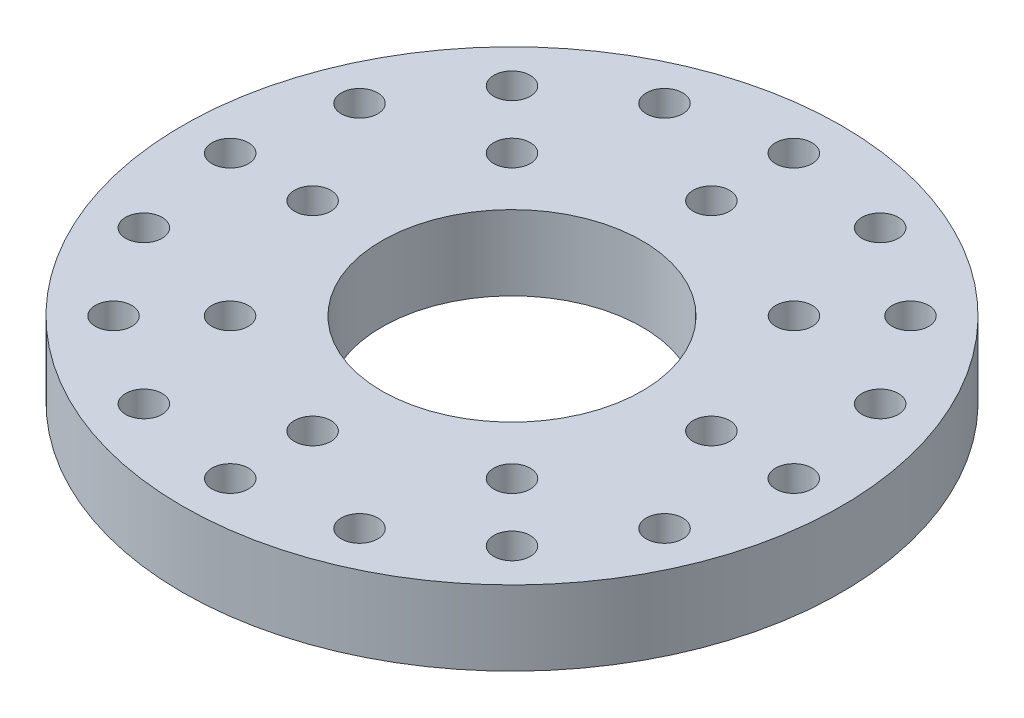
SolidWorks part; units mm, degrees
ref_plane "Front Plane" through (0, 0, 0) normal (0, 0, 1) x (1, 0, 0)
ref_plane "Top Plane" through (0, 0, 0) normal (0, 1, 0) x (1, 0, 0)
ref_plane "Right Plane" through (0, 0, 0) normal (1, 0, 0) x (0, 0, -1)
sketch "Sketch1" plane through (0, 0, 0) normal (0, 1, 0) x (1, 0, 0)
  circle A0 centre (0, 0) radius 76.2
  dimension "D1" = 152.4
extrude "Extrude1" add sketch "Sketch1" along normal blind 17.272
sketch "Sketch2" plane through (0, 0, 0) normal (0, 1, 0) x (1, 0, 0)
  circle A0 centre (0, 0) radius 30.099
  dimension "D1" = 60.198
extrude "Cut-Extrude1" cut sketch "Sketch2" along normal blind 22.352
sketch "Sketch3" plane through (0, 0, 0) normal (0, 1, 0) x (1, 0, 0)
  circle A0 centre (0, 46.101) radius 4.2164
  dimension "D1" = 46.101
  dimension "D2" = 8.4328
extrude "Cut-Extrude3" cut sketch "Sketch3" along normal blind 22.352
ref_axis "Axis1" through (0, 103.9235, 0) along (0, -1, 0)
pattern_circular "CirPattern1" count 8 over 360 about axis through (0, 103.9235, 0) along (0, -1, 0) of "Cut-Extrude3"
sketch "Sketch4" plane through (0, 0, 0) normal (0, 1, 0) x (1, 0, 0)
  circle A0 centre (0, 65.151) radius 4.2164
  dimension "D1" = 65.151
extrude "Cut-Extrude4" cut sketch "Sketch4" along normal blind 22.352
pattern_circular "CirPattern2" count 16 over 360 about axis through (0, 103.9235, 0) along (0, -1, 0) of "Cut-Extrude4"
